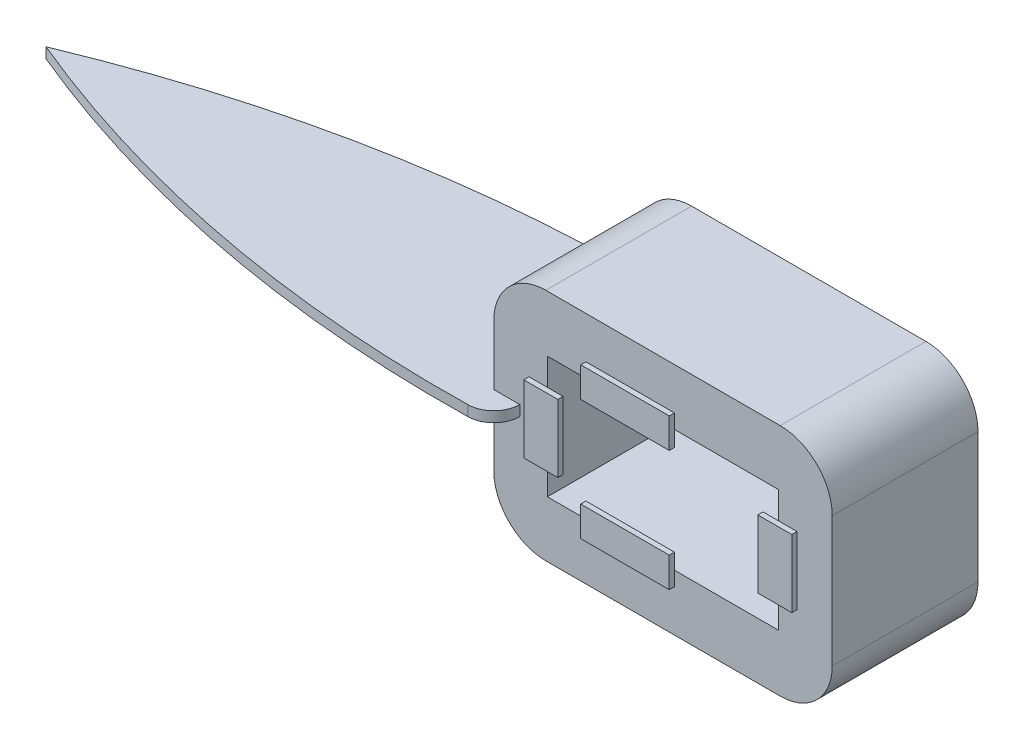
SolidWorks part; units mm, degrees
other "標示1"
sketch "草圖23" plane through (5.0653, 22.5, 33.0476) normal (0.0778, 0.9965, 0.0321) x (0.9968, -0.077, -0.0229)
ref_plane "前基準面" through (0, 0, 0) normal (0, 0, 1) x (1, 0, 0)
ref_plane "上基準面" through (0, 0, 0) normal (0, 1, 0) x (1, 0, 0)
ref_plane "右基準面" through (0, 0, 0) normal (1, 0, 0) x (0, 0, -1)
sketch "草圖1" plane through (0, 0, 0) normal (0, 0, 1) x (1, 0, 0)
  line L0 (-9.02, 0) -> (7.9922, 0) construction
  line L2 (-59.9347, 22.5) -> (5.0653, 22.5)
  line L3 (-59.9347, 22.5) -> (-59.9347, -22.5)
  line L4 (-59.9347, -22.5) -> (5.0653, -22.5)
  line L5 (5.0653, 22.5) -> (5.0653, -22.5)
  dimension "D1" = 45
  dimension "D2" = 22.5
  dimension "D3" = 65
extrude "填料-伸長1" add sketch "草圖1" along normal blind 28
sketch "草圖2" plane through (0, 0, 0) normal (0, 0, 1) x (1, 0, 0)
  line L0 (-59.9347, 0) -> (5.361, 0) construction
  line L1 (-59.9347, 22.5) -> (-59.9347, -22.5) construction
  line L2 (-27.4347, 22.5) -> (-27.4347, -22.5) construction
  line L3 (5.0653, 22.5) -> (-59.9347, 22.5) construction
  line L4 (-59.9347, -22.5) -> (5.0653, -22.5) construction
  line L6 (-49.6347, 11.7) -> (-5.2347, 11.7)
  line L7 (-49.6347, 11.7) -> (-49.6347, -11.7)
  line L8 (-49.6347, -11.7) -> (-5.2347, -11.7)
  line L9 (-5.2347, 11.7) -> (-5.2347, -11.7)
  dimension "D1" = 44.4
  dimension "D2" = 23.4
  dimension "D3" = 10.3
  dimension "D4" = 10.8
extrude "除料-伸長1" cut sketch "草圖2" along normal blind 39
ref_plane "平面1" through (0, 0, 28) normal (0, 0, 1) x (1, 0, 0)
sketch "草圖3" plane through (0, 0, 28) normal (0, 0, 1) x (1, 0, 0)
  line L0 (-59.9347, 22.5) -> (-59.9347, -22.5) construction
  line L2 (-59.9347, 12) -> (-55.9347, 12)
  line L3 (-59.9347, 12) -> (-59.9347, -12)
  line L4 (-59.9347, -12) -> (-55.9347, -12)
  line L5 (-55.9347, 12) -> (-55.9347, -12)
  line L8 (-5.2347, -11.7) -> (-49.6347, -11.7) construction
  dimension "D1" = 4
  dimension "D2" = 24
  dimension "D3" = 0.3
ref_plane "平面2" through (-59.9347, 0, 0) normal (-1, 0, 0) x (0, 0, 1)
sketch "草圖6" plane through (0, 0, 28) normal (0, 0, 1) x (1, 0, 0)
  line L0 (-15.2347, 0.3) -> (5.0653, -22.5)
  line L1 (-5.2347, 11.7) -> (-5.2347, -11.7) construction
  line L2 (-5.2347, -11.7) -> (-49.6347, -11.7) construction
  line L3 (-15.2347, 0.3) -> (-15.2347, -22.5)
  line L4 (-59.9347, -22.5) -> (5.0653, -22.5) construction
  line L5 (-15.2347, -22.5) -> (5.0653, -22.5)
  dimension "D1" = 10
  dimension "D2" = 12
ref_plane "平面4" through (0, 0, 0) normal (0, 0, -1) x (-1, 0, 0)
fillet "圓角1" radius 10 1 edges at (-59.9347, -22.5, 14) type face fillet first side face at (-59.9347, 0, 14) second side face at (-27.4347, -22.5, 14)
fillet "圓角2" radius 10 1 edges at (-59.9347, 22.5, 14) type face fillet first side face at (-27.4347, 22.5, 14) second side face at (-59.9347, 5, 14)
fillet "圓角3" radius 10 1 edges at (5.0653, 22.5, 14) type face fillet first side face at (-22.4347, 22.5, 14) second side face at (5.0653, 0, 14)
fillet "圓角4" radius 10 1 edges at (5.0653, -22.5, 14) type face fillet first side face at (-22.4347, -22.5, 14) second side face at (5.0653, -5, 14)
ref_plane "平面6" through (0, 0, 29) normal (0, 0, 1) x (1, 0, 0)
sketch "草圖10" plane through (0, 0, 29) normal (0, 0, 1) x (1, 0, 0)
  line L6 (-49.6347, 0) -> (-4.2092, 0) construction
  line L7 (-49.6347, -11.7) -> (-49.6347, 11.7) construction
  line L8 (-27.4347, -11.7) -> (-27.4347, 19.297) construction
  line L9 (-5.2347, -11.7) -> (-49.6347, -11.7) construction
  line L11 (-49.6347, 6.5) -> (-53.1651, 6.5)
  line L14 (-53.1651, 6.5) -> (-53.1651, -6.5)
  line L17 (-49.6347, 6.5) -> (-46.6347, 6.5)
  line L18 (-46.6347, 6.5) -> (-46.6347, -6.5)
  line L20 (-42.2347, -11.7) -> (-42.2347, -8.7)
  line L25 (-42.2347, -11.7) -> (-42.2347, -14.4546)
  line L27 (-8.2347, 6.5) -> (-8.2347, -6.5)
  line L28 (-8.2347, -6.5) -> (-5.2347, -6.5)
  line L29 (-5.2347, -6.5) -> (-1.7043, -6.5)
  line L30 (-1.7043, 6.5) -> (-1.7043, -6.5)
  line L32 (-25.2347, 8.7) -> (-25.2347, 14.4546)
  line L33 (-25.2347, -14.4546) -> (-25.2347, -8.7)
  line L34 (-25.2347, -14.4546) -> (-42.2347, -14.4546)
  line L35 (-25.2347, -8.7) -> (-42.2347, -8.7)
  line L36 (-25.2347, 8.7) -> (-42.2347, 8.7)
  line L37 (-25.2347, 14.4546) -> (-42.2347, 14.4546)
  line L38 (-42.2347, 8.7) -> (-42.2347, 14.4546)
  line L39 (-46.6347, -6.5) -> (-53.1651, -6.5)
  line L40 (-1.7043, 6.5) -> (-8.2347, 6.5)
  dimension "D3" = 13
  dimension "D4" = 6.5
extrude "填料-伸長6" add sketch "草圖10" against normal blind 1 separate body
sketch "草圖19" plane through (0, 0, 0) normal (0, 1, 0) x (1, 0, 0)
  line L0 (-59.9347, 6.325) -> (-59.9347, -6.325) construction
  line L1 (-59.9347, 1.0971) -> (-54.9347, 1.0971)
  line L2 (-59.9347, 1.0971) -> (-59.9347, -29)
  line L3 (-59.9347, -29) -> (-54.9347, -29)
  line L4 (-54.9347, 1.0971) -> (-54.9347, -29)
  line L5 (-24.75, -29) -> (24.75, -29) construction
  dimension "D1" = 5
ref_plane "平面7" through (0, 0, 28) normal (0, 0, 1) x (1, 0, 0)
sketch "草圖20" plane through (0, 0, 28) normal (0, 0, 1) x (1, 0, 0)
  line L0 (-59.9347, 12.5) -> (-59.9347, -12.5) construction
  line L1 (-59.9347, 1) -> (-54.932, 1)
  line L2 (-59.9347, 1) -> (-59.9347, -1)
  line L3 (-59.9347, -1) -> (-54.932, -1)
  line L4 (-54.932, 1) -> (-54.932, -1)
  line L5 (-59.9347, 0) -> (-54.9347, 0) construction
  dimension "D1" = 5.0026
  dimension "D2" = 2
  dimension "D3" = 1
extrude "填料-伸長7" add sketch "草圖20" along normal blind 5
ref_plane "平面8" through (0, 0, 0) normal (0, 0, -1) x (-1, 0, 0)
sketch "草圖21" plane through (0, 0, 0) normal (0, 0, -1) x (-1, 0, 0)
  line L0 (59.9347, 0) -> (54.9347, 0) construction
  line L1 (54.9323, 1) -> (59.9347, 1)
  line L2 (54.9323, 1) -> (54.9323, -1)
  line L3 (54.9323, -1) -> (59.9347, -1)
  line L4 (59.9347, 1) -> (59.9347, -1)
  dimension "D1" = 5.0023
  dimension "D2" = 2
  dimension "D3" = 1
extrude "填料-伸長8" add sketch "草圖21" along normal blind 5
sketch "草圖22" plane through (0, 0, 0) normal (0, 1, 0) x (1, 0, 0)
  line L1 (-59.9347, 5) -> (-59.9347, -33)
  line L2 (-59.9347, -14) -> (-159.9347, -14) construction
  arc A2 (-159.9347, -14) -> (-59.9347, 5) centre (-64.7845, -242.1324) cw
  arc A3 (-159.9347, -14) -> (-59.9347, -33) centre (-64.7845, 214.1324) ccw
  dimension "D2" = 247.18
  dimension "D3" = 247.18
  dimension "D1" = 100
extrude "填料-伸長9" add sketch "草圖22" along normal blind 1 and the other way blind 1
fillet "圓角5" radius 5 1 edges at (-54.9323, 0, -5) type face fillet first side face at (-57.4335, 0, -5) second side face at (-54.9323, 0, -2.5)
fillet "圓角6" radius 5 1 edges at (-54.932, 0, 33) type face fillet first side face at (-57.4333, 0, 33) second side face at (-54.932, 0, 30.5)
